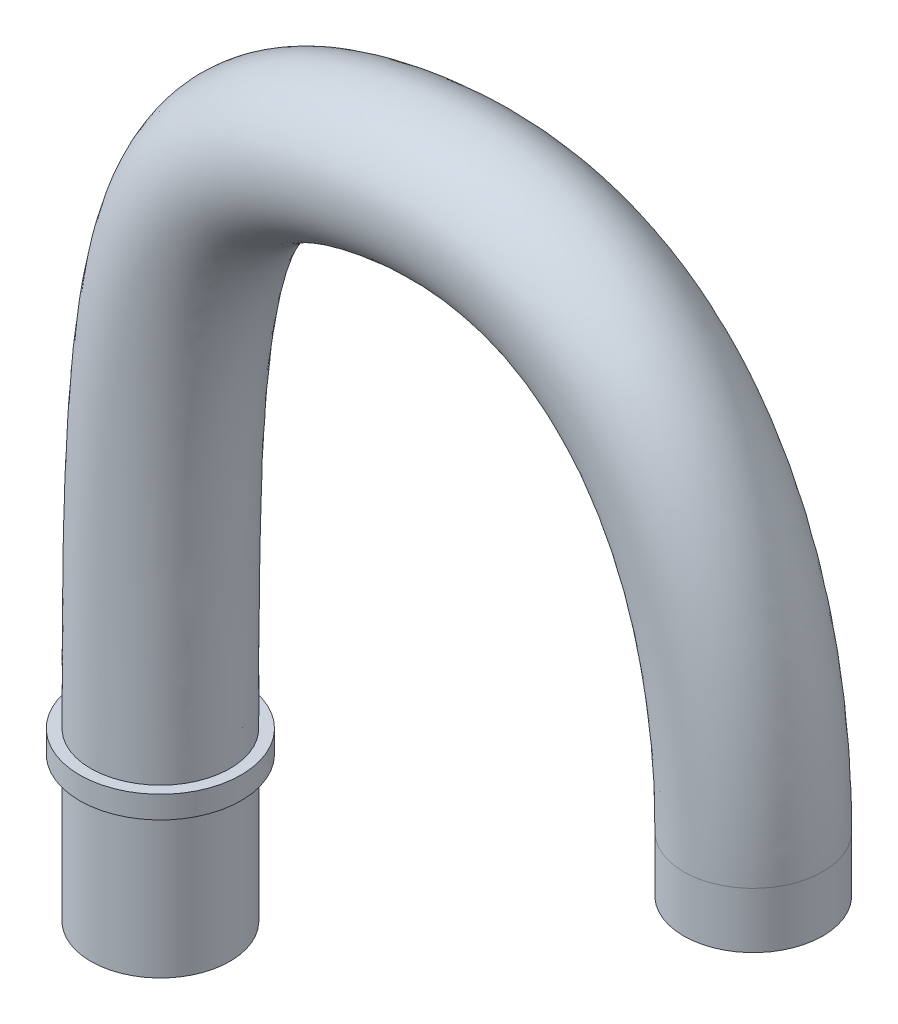
SolidWorks part; units mm, degrees
ref_plane "Płaszczyzna przednia" through (0, 0, 0) normal (0, 0, 1) x (1, 0, 0)
ref_plane "Płaszczyzna górna" through (0, 0, 0) normal (0, 1, 0) x (1, 0, 0)
ref_plane "Płaszczyzna prawa" through (0, 0, 0) normal (1, 0, 0) x (0, 0, -1)
sketch "Sketch1" plane through (0, 0, 0) normal (0, 0, 1) x (1, 0, 0)
  line L1 (25.5636, 41.2004) -> (0.3636, 41.2004) construction
  spline S0 degree 3 poles (-93.5364, 0) (-93.5364, 68.8979) (-92.6957, 106.938) (-8.9755, 119.82) (12.9636, 82.9446) (12.9636, 41.2004) knots 0 0 0 0 0.466992 0.566992 1 1 1 1
sketch "Sketch2" plane through (0, 0, 0) normal (0, 1, 0) x (1, 0, 0)
  circle A0 centre (-93.5364, 0) radius 12.5
  circle A2 centre (-93.5364, 0) radius 10.5
  dimension "D2" = 25
  dimension "D1" = 2
sweep "Sweep1" add profiles "Sketch2" path "Sketch1"
extrude "Boss-Extrude1" add sketch "Sketch2<2>" against normal blind 26 contours A0 | A2
sketch "Sketch2<2>" plane through (0, 0, 0) normal (0, 1, 0) x (1, 0, 0) same geometry as "Sketch2"
sketch "Sketch5" plane through (0, 0, 0) normal (0, 1, 0) x (1, 0, 0)
  circle A0 centre (-93.5364, 0) radius 14.5
  circle A1 centre (-93.5364, 0) radius 12.5 construction
  circle A2 centre (-93.5364, 0) radius 11.5969
  dimension "D1" = 2
extrude "Boss-Extrude5" add sketch "Sketch5" along normal blind 4
sketch "Sketch6" plane through (0, 41.2004, 0) normal (0, -1, 0) x (1, 0, 0)
  circle A0 centre (12.9636, 0) radius 12.5
  circle A1 centre (12.9636, 0) radius 10.5
  dimension "D1" = 2
extrude "Boss-Extrude6" add sketch "Sketch6" along normal blind 10
